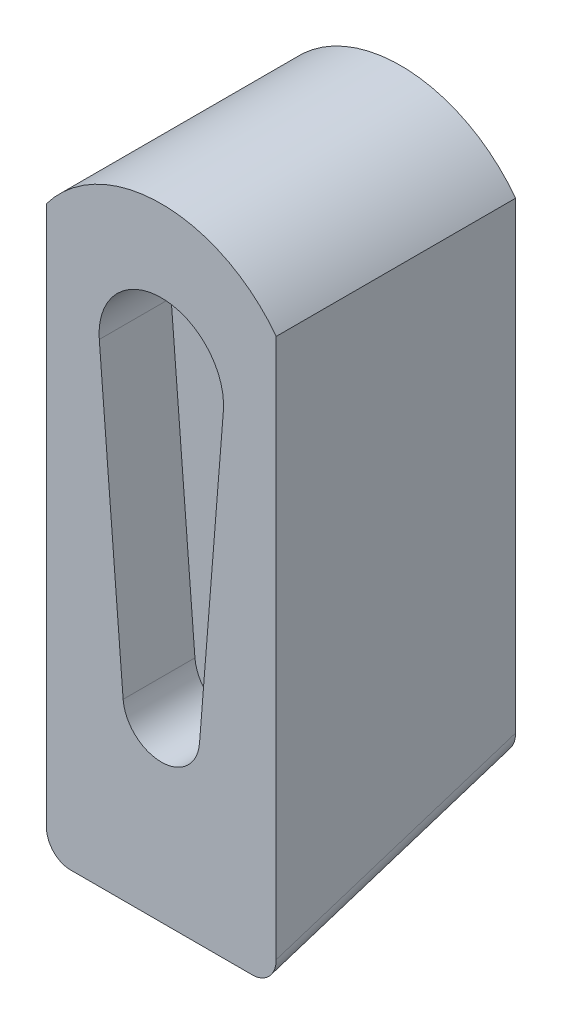
SolidWorks part; units mm, degrees
material "ABS"
ref_plane "Front Plane" through (0, 0, 0) normal (0, 0, 1) x (1, 0, 0)
ref_plane "Top Plane" through (0, 0, 0) normal (0, 1, 0) x (1, 0, 0)
ref_plane "Right Plane" through (0, 0, 0) normal (1, 0, 0) x (0, 0, -1)
sketch "Sketch1" plane through (0, 0, 0) normal (0, 0, 1) x (1, 0, 0)
  line L0 (-6.096, 4.572) -> (-6.096, -33.528)
  line L1 (-6.096, -33.528) -> (6.096, -33.528)
  line L2 (6.096, -33.528) -> (6.096, 4.572)
  arc A0 (-6.096, 4.572) -> (6.096, 4.572) centre (0, 0) cw
  point P7 (0, -33.528)
  dimension "D1" = 7.62
  dimension "D3" = 38.1
  dimension "D2" = 12.192
extrude "Boss-Extrude1" add sketch "Sketch1" along normal blind 12.7
sketch "Sketch2" plane through (0, 0, 12.7) normal (0, 0, 1) x (1, 0, 0)
  line L0 (3.2916, -0.2621) -> (2.0256, -16.1633)
  line L1 (-2.0256, -16.1633) -> (-3.2916, -0.2621)
  arc A0 (3.2916, -0.2621) -> (-3.2916, -0.2621) centre (0, 0) ccw
  arc A1 (2.0256, -16.1633) -> (-2.0256, -16.1633) centre (0, -16.002) cw
  dimension "D1" = 3.302
  dimension "D2" = 2.032
  dimension "D3" = 16.002
extrude "Cut-Extrude1" cut sketch "Sketch2" against normal blind 3.81 and the other way through all
sketch "Sketch3" plane through (6.096, 0, 0) normal (1, 0, 0) x (0, 0, -1)
  line L0 (-12.7, -33.528) -> (-12.7, 4.572) construction
  line L1 (-12.7, -33.528) -> (-12.7, -25.4)
  line L2 (-12.7, -25.4) -> (0, -21.336)
  line L3 (0, -33.528) -> (0, 4.572) construction
  line L4 (0, -21.336) -> (0, -33.528)
  line L5 (0, -33.528) -> (-12.7, -33.528)
  dimension "D1" = 8.128
  dimension "D2" = 12.192
extrude "Cut-Extrude2" cut sketch "Sketch3" against normal through all
sketch "Sketch4" plane through (0, 0, 8.89) normal (0, 0, 1) x (1, 0, 0)
  circle A0 centre (0, 0) radius 1.5875
  dimension "D1" = 3.175
extrude "Cut-Extrude3" cut sketch "Sketch4" against normal through all
sketch "Sketch5" plane through (0, 0, 0) normal (0, 0, -1) x (-1, 0, 0)
  circle A0 centre (0, 0) radius 3.175
  dimension "D1" = 6.35
extrude "Cut-Extrude4" cut sketch "Sketch5" against normal blind 6.35
chamfer "Chamfer1" distance 1.016 angle 45 1 edges at (-3.175, 0, 6.35)
fillet "Fillet1" radius 1.27 2 edges at (-6.096, -23.368, 6.35) (6.096, -23.368, 6.35)
